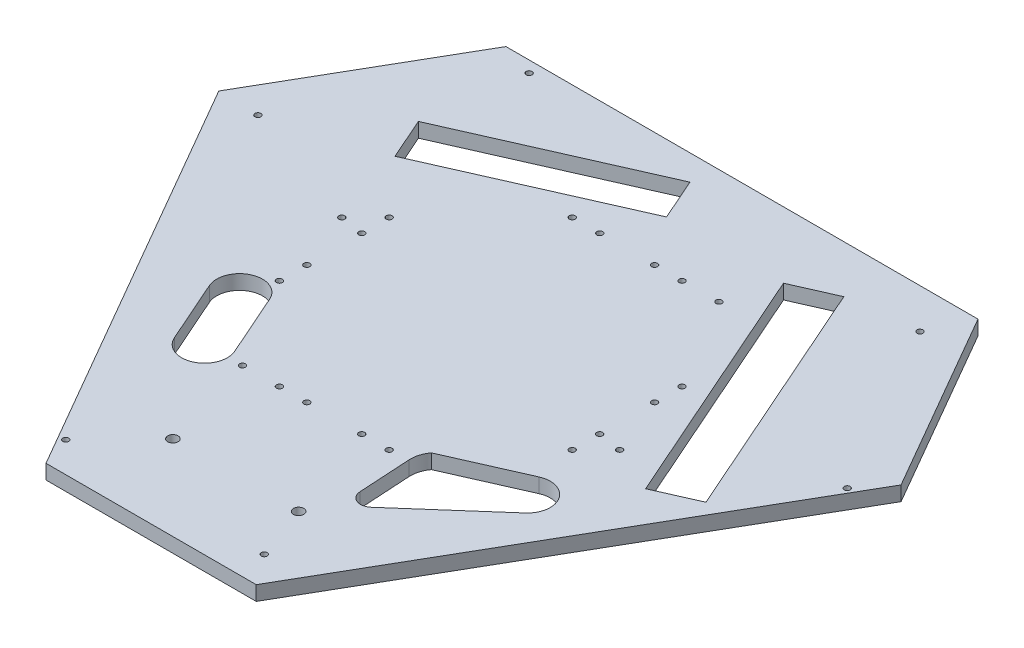
SolidWorks part; units mm, degrees
material "Pin"
ref_plane "Plan de face" through (0, 0, 0) normal (0, 0, 1) x (1, 0, 0)
ref_plane "Plan de dessus" through (0, 0, 0) normal (0, 1, 0) x (1, 0, 0)
ref_plane "Plan de droite" through (0, 0, 0) normal (1, 0, 0) x (0, 0, -1)
sketch "BB_position" plane through (0, 0, 0) normal (0, 1, 0) x (1, 0, 0)
  line L0 (-110, 63.5085) -> (110, 63.5085) construction
  line L7 (110, 63.5085) -> (0, -127.0171) construction
  line L8 (0, -127.0171) -> (-110, 63.5085) construction
  circle A0 centre (0, 0) radius 127.0171 construction
  circle A1 centre (-110, 63.5085) radius 5 construction
  circle A2 centre (110, 63.5085) radius 5 construction
  circle A3 centre (0, -127.0171) radius 5 construction
  dimension "D1" = 220
  dimension "D2" = 10
sketch "BB_Footprint" plane through (0, 0, 0) normal (0, 1, 0) x (1, 0, 0)
  line L0 (-110, 63.5085) -> (-128.115, 32.1324) construction
  line L1 (-128.115, 32.1324) -> (-131.4232, 34.0424) construction
  line L2 (-131.4232, 34.0424) -> (-88.0354, 109.1924) construction
  line L3 (95.1932, 96.7946) -> (138.5811, 21.6447) construction
  line L4 (110, 63.5085) -> (91.885, 94.8846) construction
  line L5 (91.885, 94.8846) -> (95.1932, 96.7946) construction
  line L6 (36.23, -130.8371) -> (-50.5457, -130.8371) construction
  line L7 (0, -127.0171) -> (36.23, -127.0171) construction
  line L8 (36.23, -127.0171) -> (36.23, -130.8371) construction
  circle A0 centre (-110, 63.5085) radius 5 construction
  circle A1 centre (0, 0) radius 127.0171 construction
  circle A2 centre (-110, 63.5085) radius 5 construction
  circle A3 centre (110, 63.5085) radius 5 construction
  circle A4 centre (0, -127.0171) radius 5 construction
  point P23 (0, 0)
  dimension "D1" = 3.82
  dimension "D2" = 36.23
  dimension "D3" = 86.7757
  dimension "D4" = 3
sketch "Esquisse3" plane through (0, 0, 0) normal (0, 1, 0) x (1, 0, 0)
  line L0 (-103.1624, 114.1924) -> (103.1624, 114.1924)
  line L1 (-103.1624, 114.1924) -> (-149.104, 34.6191)
  line L2 (-149.104, 34.6191) -> (-45.9416, -144.0633)
  line L3 (-45.9416, -144.0633) -> (45.9416, -144.0633)
  line L4 (45.9416, -144.0633) -> (149.104, 34.6191)
  line L5 (149.104, 34.6191) -> (103.1624, 114.1924)
  line L6 (-131.4232, 34.0424) -> (-88.0354, 109.1924) construction
  point P2 (0, 114.1924)
  point P7 (0, -144.0633)
  point P9 (59.6843, -147.0192)
  point P12 (180.4991, 48.7095)
  point P13 (47.9558, -195.1127)
  point P14 (40.7327, -192.5559)
  point P16 (-154.1995, 33.8406)
  dimension "D1" = 5
sketch "TB_boltPattern" plane through (0, 0, 0) normal (0, 1, 0) x (1, 0, 0)
  line L0 (0, 143.3581) -> (0, -141.7362) construction
  line L1 (-23, 57.7) -> (-13, 57.7) construction
  line L2 (-23, 57.7) -> (-23, 43.7) construction
  line L3 (-23, 43.7) -> (-13, 43.7) construction
  line L4 (-13, 57.7) -> (-13, 43.7) construction
  line L5 (-57.7, 23) -> (-43.7, 23) construction
  line L6 (-57.7, 23) -> (-57.7, 13) construction
  line L7 (-57.7, 13) -> (-43.7, 13) construction
  line L8 (-43.7, 23) -> (-43.7, 13) construction
  line L9 (-204.4729, 0) -> (279.6048, 0) construction
  circle A0 centre (-24, 64) radius 1.6 construction
  circle A1 centre (-12, 64) radius 1.6 construction
  circle A2 centre (-64, 24) radius 1.6 construction
  circle A3 centre (-64, 12) radius 1.6 construction
  point P8 (-18, 57.7)
  dimension "D5" = 3.2
  dimension "D10" = 6.3
  dimension "D1" = 12
  dimension "D2" = 12
  dimension "D3" = 40
  dimension "D4" = 40
  dimension "D6" = 14
  dimension "D7" = 10
  dimension "D8" = 1
  dimension "D9" = 6.3
  dimension "D11" = 1
  dimension "D12" = 12
  dimension "D13" = 12
extrude "Boss.-Extru.1" add sketch "Esquisse3" against normal blind 6.35
hole_wizard "BBCase_boltPattern" positions "Esquisse6" profile "Esquisse8" hole size "M3" standard "Ansi Metric"
sketch "Esquisse6" plane through (0, 0, 0) normal (0, 1, 0) x (1, 0, 0)
  point P0 (-88.0354, 109.1924)
  point P3 (-131.4232, 34.0424)
sketch "Esquisse8" plane through (-88.0354, 0, -109.1924) normal (1, 0, 0) x (0, 0, 1)
  line L0 (0, 0) -> (0, 7.1311)
  line L1 (0, 7.1311) -> (1.3, 6.35)
  line L2 (1.3, 6.35) -> (1.3, 0)
  line L5 (1.3, 0) -> (0, 0)
  line L10 (0, 7.1311) -> (-1.3, 6.35) construction
  line L11 (0, -6.35) -> (0, 107.95) construction
  dimension "Diamètre du perçage" = 2.6
  dimension "Profondeur du perçage" = 6.35
  dimension "Angle de pointe" = 118
ref_axis "Axe1" through (0, 0, 0) along (0, 1, 0)
pattern_circular "Répétition circulaire1" count 3 over 360 about axis through (0, 0, 0) along (0, 1, 0) of "BBCase_boltPattern"
hole_wizard "Dégagement M32" positions "Esquisse9" profile "Esquisse10" hole size "M3" standard "Ansi Metric"
sketch "Esquisse9" plane through (0, 0, 0) normal (0, 1, 0) x (1, 0, 0)
  point P0 (-24, 64)
  point P3 (-12, 64)
  point P6 (-64, 24)
  point P9 (-64, 12)
sketch "Esquisse10" plane through (-24, 0, -64) normal (1, 0, 0) x (0, 0, 1)
  line L0 (0, 0) -> (0, 7.1311)
  line L1 (0, 7.1311) -> (1.3, 6.35)
  line L2 (1.3, 6.35) -> (1.3, 0)
  line L5 (1.3, 0) -> (0, 0)
  line L10 (0, 7.1311) -> (-1.3, 6.35) construction
  line L11 (0, -6.35) -> (0, 107.95) construction
  dimension "Diamètre du perçage" = 2.6
  dimension "Profondeur du perçage" = 6.35
  dimension "Angle de pointe" = 118
pattern_circular "Répétition circulaire2" count 4 over 360 about axis through (0, 0, 0) along (0, 1, 0) of "Dégagement M32"
sketch "HB_Footprint" plane through (0, 0, 0) normal (0, 1, 0) x (1, 0, 0)
  line L0 (-74.3426, 13.6262) -> (40.0015, 64.1278) construction
  line L1 (40.0015, 64.1278) -> (74.3426, -13.6262) construction
  line L2 (-74.3426, 13.6262) -> (-40.0015, -64.1278) construction
  line L3 (-40.0015, -64.1278) -> (74.3426, -13.6262) construction
  line L8 (-77.8072, 30.1336) -> (-30.1336, -77.8072) construction
  line L9 (-30.1336, -77.8072) -> (77.8072, -30.1336) construction
  line L10 (77.8072, -30.1336) -> (30.1336, 77.8072) construction
  line L11 (-77.8072, 30.1336) -> (30.1336, 77.8072) construction
  line L12 (-23.8368, 53.9704) -> (23.8368, -53.9704) construction
  line L13 (-57.1721, -25.2508) -> (0, 0) construction
  circle A0 centre (-74.3426, 13.6262) radius 1.6 construction
  circle A1 centre (40.0015, 64.1278) radius 1.6 construction
  circle A2 centre (-40.0015, -64.1278) radius 1.6 construction
  circle A3 centre (74.3426, -13.6262) radius 1.6 construction
  point P10 (23.8368, -53.9704)
  point P17 (-120.167, -142.0148)
  point P18 (-159.407, -71.6253)
  point P19 (-17.1706, 38.877)
  point P20 (-51.4076, -143.7608)
  point P21 (-163.89, -101.7836)
  point P22 (0, 0)
  point P24 (-82.7143, -10.9704)
  point P25 (0, 0)
  point P26 (0, 0)
  point P27 (83.2156, -6.0967)
  point P28 (63.328, 54.3283)
  point P29 (30.1336, 77.8072)
  dimension "D4" = 3.2
  dimension "D1" = 125
  dimension "D2" = 85
  dimension "D3" = 118
hole_wizard "Dégagement M33" positions "Esquisse11" profile "Esquisse12" hole size "M3" standard "Ansi Metric"
sketch "Esquisse11" plane through (0, 0, 0) normal (0, 1, 0) x (1, 0, 0)
  point P0 (-74.3426, 13.6262)
  point P3 (-40.0015, -64.1278)
  point P6 (74.3426, -13.6262)
  point P9 (40.0015, 64.1278)
sketch "Esquisse12" plane through (-74.3426, 0, -13.6262) normal (1, 0, 0) x (0, 0, 1)
  line L0 (0, 0) -> (0, 7.1311)
  line L1 (0, 7.1311) -> (1.3, 6.35)
  line L2 (1.3, 6.35) -> (1.3, 0)
  line L5 (1.3, 0) -> (0, 0)
  line L10 (0, 7.1311) -> (-1.3, 6.35) construction
  line L11 (0, -6.35) -> (0, 107.95) construction
  dimension "Diamètre du perçage" = 2.6
  dimension "Profondeur du perçage" = 6.35
  dimension "Angle de pointe" = 118
sketch "Esquisse13" plane through (0, 0, 0) normal (0, 1, 0) x (1, 0, 0)
  line L0 (113.0252, -14.5791) -> (94.7302, -22.6594)
  line L1 (94.7302, -22.6594) -> (47.0566, 85.2815)
  line L2 (47.0566, 85.2815) -> (65.3516, 93.3617)
  line L3 (65.3516, 93.3617) -> (113.0252, -14.5791)
  line L5 (-77.8072, 30.1336) -> (30.1336, 77.8072) construction
  line L7 (40.0015, 64.1278) -> (74.3426, -13.6262) construction
  line L13 (-30.1336, -77.8072) -> (77.8072, -30.1336) construction
  line L14 (-11.64, 103.085) -> (-93.9678, 66.7238)
  line L15 (-93.9678, 66.7238) -> (-85.8875, 48.4287)
  line L16 (-85.8875, 48.4287) -> (-3.5597, 84.7899)
  line L17 (-3.5597, 84.7899) -> (-11.64, 103.085)
  line L18 (-77.8072, 30.1336) -> (-30.1336, -77.8072) construction
  point P20 (-19.4359, 105.6193)
  dimension "D1" = 15
  dimension "D2" = 20
  dimension "D5" = 20
  dimension "D6" = 90
  dimension "D7" = 20
extrude "Enlèv. mat.-Extru.1" cut sketch "Esquisse13" against normal up to surface (6.35 mm away) up to face at (-74.3426, -6.35, -12.3262)
sketch "Esquisse15" plane through (0, 0, 0) normal (0, 1, 0) x (1, 0, 0)
  line L0 (-27.48, -107.0633) -> (27.48, -107.0633) construction
  line L1 (0, 200143.3581) -> (0, -200141.7362) construction
  line L2 (-45.9416, -144.0633) -> (45.9416, -144.0633) construction
  circle A0 centre (-27.48, -107.0633) radius 3.5746 construction
  circle A1 centre (27.48, -107.0633) radius 3.5746 construction
  point P4 (0, -107.0633)
  dimension "D1" = 54.96
  dimension "D2" = 37
hole_wizard "Dégagement M51" positions "Esquisse16" profile "Esquisse17" hole size "M5" standard "Ansi Metric"
sketch "Esquisse16" plane through (0, 0, 0) normal (0, 1, 0) x (1, 0, 0)
  point P0 (-27.48, -107.0633)
  point P3 (27.48, -107.0633)
sketch "Esquisse17" plane through (-27.48, 0, 107.0633) normal (1, 0, 0) x (0, 0, 1)
  line L0 (0, 0) -> (0, 7.714)
  line L1 (0, 7.714) -> (2.27, 6.35)
  line L2 (2.27, 6.35) -> (2.27, 0)
  line L5 (2.27, 0) -> (0, 0)
  line L10 (0, 7.714) -> (-2.27, 6.35) construction
  line L11 (0, -6.35) -> (0, 107.95) construction
  dimension "Diamètre du perçage" = 4.54
  dimension "Profondeur du perçage" = 6.35
  dimension "Angle de pointe" = 118
sketch "Esquisse18" plane through (0, 0, 0) normal (0, 1, 0) x (1, 0, 0)
  line L0 (71.0075, -50.6279) -> (43.5649, -62.7483) construction
  line L2 (66.9674, -41.4803) -> (34.336, -55.8925)
  line L3 (-30.1336, -77.8072) -> (77.8072, -30.1336) construction
  line L4 (23.8368, -53.9704) -> (77.8072, -30.1336) construction
  line L5 (50.822, -42.052) -> (57.2862, -56.6881) construction
  line L6 (-68.3683, -37.0282) -> (-56.2479, -64.4708) construction
  line L7 (-59.2207, -32.9881) -> (-47.1003, -60.4307)
  line L8 (-77.5158, -41.0684) -> (-65.3954, -68.511)
  line L9 (-74.3426, 13.6262) -> (-40.0015, -64.1278) construction
  line L10 (-57.1721, -25.2508) -> (-40.0015, -64.1278) construction
  line L11 (-48.5868, -44.6893) -> (-62.3081, -50.7495) construction
  line L12 (32.0883, -63.4284) -> (33.4385, -86.2128)
  line L13 (41.7305, -89.6726) -> (77.6091, -58.1391)
  arc A0 (77.6091, -58.1391) -> (66.9674, -41.4803) centre (71.0075, -50.6279) ccw
  arc A1 (34.336, -55.8925) -> (32.0883, -63.4284) centre (43.5649, -62.7483) ccw
  arc A2 (-59.2207, -32.9881) -> (-77.5158, -41.0684) centre (-68.3683, -37.0282) ccw
  arc A3 (-65.3954, -68.511) -> (-47.1003, -60.4307) centre (-56.2479, -64.4708) ccw
  arc A4 (33.4385, -86.2128) -> (41.7305, -89.6726) centre (38.4297, -85.917) ccw
  point P2 (57.2862, -56.6881)
  point P3 (0, 0)
  point P4 (33.9885, -62.6231)
  point P16 (-62.3081, -50.7495)
  point P31 (0, 0)
  point P35 (34.0438, -96.4284)
  dimension "D4" = 15
  dimension "D6" = 10
  dimension "D1" = 10
  dimension "D11" = 5
  dimension "D2" = 6
  dimension "D3" = 30
  dimension "D5" = 30
  dimension "D7" = 35
  dimension "D8" = 58
  dimension "D9" = 10
  dimension "D10" = 33
extrude "Enlèv. mat.-Extru.3" cut sketch "Esquisse18" against normal up to surface (6.35 mm away) up to face at (-27.48, -6.35, 109.3333)
